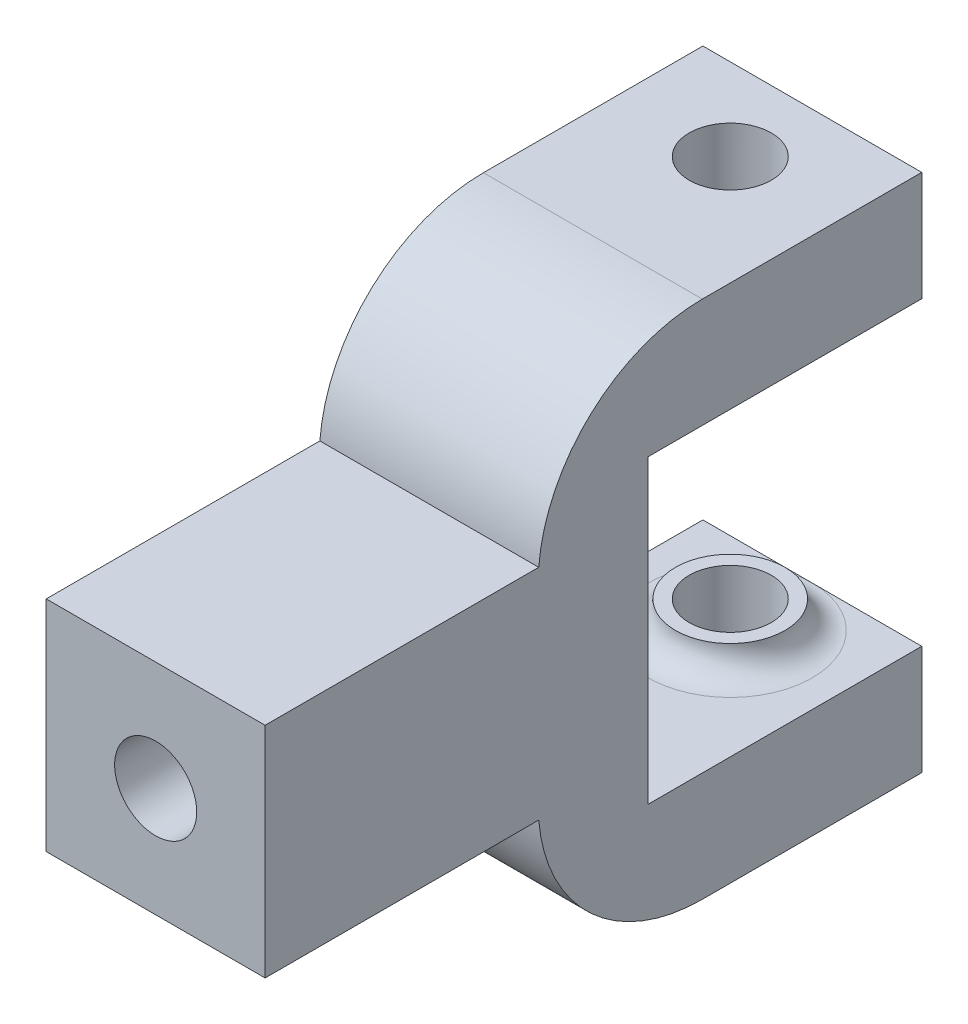
SolidWorks part; units mm, degrees
ref_plane "Спереди" through (0, 0, 0) normal (0, 0, 1) x (1, 0, 0)
ref_plane "Сверху" through (0, 0, 0) normal (0, 1, 0) x (1, 0, 0)
ref_plane "Справа" through (0, 0, 0) normal (1, 0, 0) x (0, 0, -1)
sketch "Эскиз3" plane through (0, 0, 0) normal (1, 0, 0) x (0, 0, -1)
  line L0 (0, 0) -> (14, 0)
  line L1 (14, 0) -> (14, 4)
  line L2 (14, 4) -> (4, 4)
  line L3 (4, 4) -> (4, 15)
  line L4 (4, 15) -> (14, 15)
  line L5 (14, 15) -> (14, 19)
  line L6 (14, 19) -> (0, 19)
  line L7 (0, 19) -> (0, 0)
  dimension "D1" = 4
  dimension "D2" = 4
  dimension "D3" = 11
  dimension "D4" = 10
  dimension "D5" = 4
  dimension "D6" = 14
extrude "Бобышка-Вытянуть1" add sketch "Эскиз3" along normal blind 8
sketch "Эскиз4" plane through (0, 19, 0) normal (0, 1, 0) x (1, 0, 0)
  line L0 (4, 14) -> (4, 0) construction
  line L1 (8, 14) -> (0, 14) construction
  line L2 (8, 0) -> (0, 0) construction
  circle A0 centre (4, 11) radius 1.5
  dimension "D2" = 3
  dimension "D1" = 3
extrude "Вырез-Вытянуть1" cut sketch "Эскиз4" against normal up to surface (19 mm away) up to face at (4, 0, -7)
sketch "Эскиз5" plane through (0, 4, 0) normal (0, 1, 0) x (1, 0, 0)
  circle A0 centre (4, 11) radius 2
  circle A1 centre (4, 11) radius 1.5
  dimension "D1" = 4
  dimension "D2" = 3
extrude "Бобышка-Вытянуть2" add sketch "Эскиз5" along normal blind 1
sketch "Эскиз6" plane through (0, 15, 0) normal (0, -1, 0) x (-1, 0, 0)
  circle A0 centre (-4, 11) radius 2
  circle A1 centre (-4, 11) radius 1.5
  dimension "D1" = 4
  dimension "D2" = 3
extrude "Бобышка-Вытянуть3" add sketch "Эскиз6" along normal blind 1
fillet "Скругление1" radius 1 1 edges at (4, 4, -13)
fillet "Скругление2" radius 1 1 edges at (4, 15, -9)
sketch "Эскиз10" plane through (0, 0, 0) normal (0, 0, 1) x (1, 0, 0)
  line L0 (8, 13.5) -> (0, 13.5)
  line L1 (8, 19) -> (8, 0) construction
  line L2 (0, 19) -> (0, 0) construction
  line L3 (0, 13.5) -> (0, 5.5)
  line L4 (0, 5.5) -> (8, 5.5)
  line L5 (8, 5.5) -> (8, 13.5)
  line L6 (4, 19) -> (4, 0) construction
  line L7 (8, 19) -> (0, 19) construction
  line L8 (8, 0) -> (0, 0) construction
  line L9 (2.2308, 9.5) -> (5.8965, 9.5) construction
  dimension "D1" = 8
extrude "Бобышка-Вытянуть5" add sketch "Эскиз10" along normal blind 10
sketch "Эскиз7" plane through (0, 0, -4) normal (0, 0, -1) x (-1, 0, 0)
  line L0 (-8, 9.5) -> (0, 9.5) construction
  line L1 (-8, 4) -> (-8, 15) construction
  line L2 (0, 4) -> (0, 15) construction
  line L3 (-4, 15) -> (-4, 4) construction
  line L4 (-8, 15) -> (0, 15) construction
  line L5 (-8, 4) -> (0, 4) construction
  circle A0 centre (-4, 9.5) radius 1.5
  dimension "D1" = 3
extrude "Вырез-Вытянуть2" cut sketch "Эскиз7" against normal up to surface (14 mm away) up to face at (4, 9.5, 10)
sketch "Эскиз9" plane through (0, 0, -4) normal (0, 0, -1) x (-1, 0, 0)
  line L1 (-1.2641, 11.1119) -> (-4.028, 12.6753)
  line L2 (-4.028, 12.6753) -> (-6.7639, 11.0634)
  line L3 (-6.7639, 11.0634) -> (-6.7359, 7.8881)
  line L4 (-6.7359, 7.8881) -> (-3.972, 6.3247)
  line L5 (-3.972, 6.3247) -> (-1.2361, 7.9366)
  line L6 (-1.2361, 7.9366) -> (-1.2641, 11.1119)
  circle A0 centre (-4, 9.5) radius 2.75 construction
  dimension "D1" = 5.5
extrude "Вырез-Вытянуть3" cut sketch "Эскиз9" against normal offset from surface (10 mm away) 4 up to face at (5.5, 9.5, 10)
fillet "Скругление3" radius 6 1 edges at (4, 19, 0)
fillet "Скругление4" radius 6 1 edges at (4, 0, 0)
